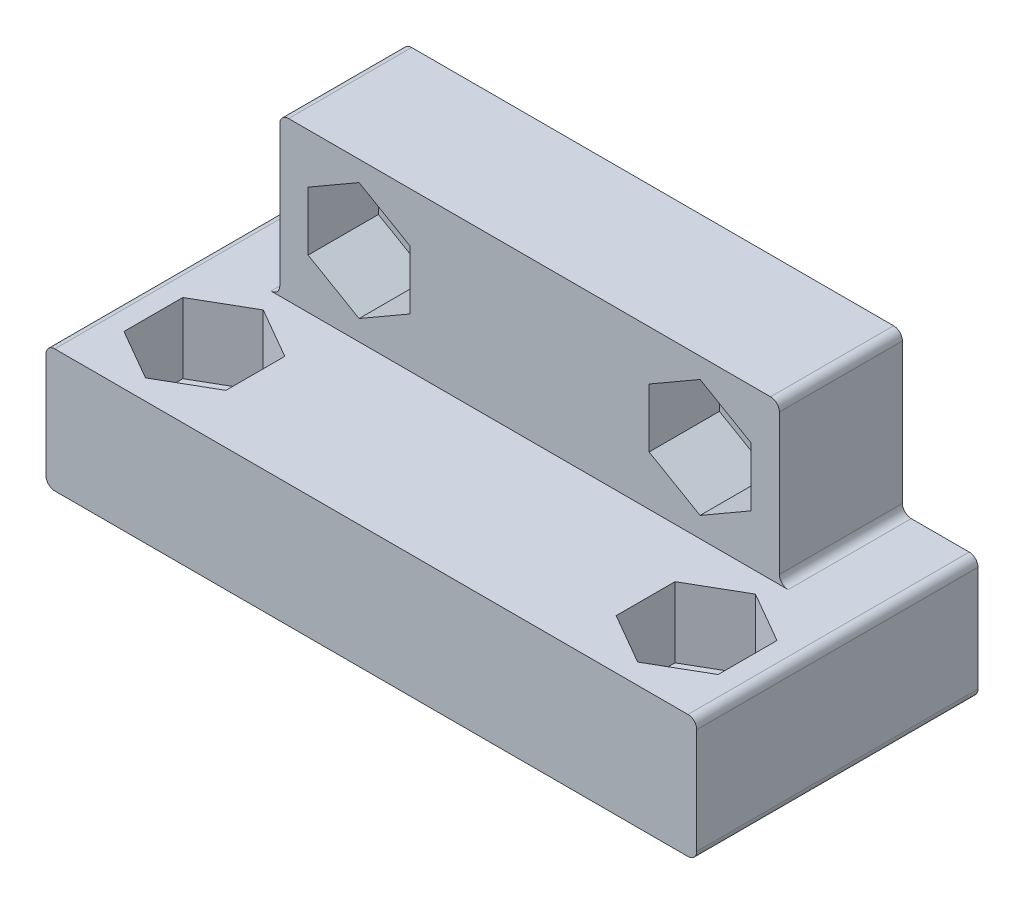
SolidWorks part; units mm, degrees
ref_plane "Front Plane" through (0, 0, 0) normal (0, 0, 1) x (1, 0, 0)
ref_plane "Top Plane" through (0, 0, 0) normal (0, 1, 0) x (1, 0, 0)
ref_plane "Right Plane" through (0, 0, 0) normal (1, 0, 0) x (0, 0, -1)
sketch "Sketch1" plane through (0, 0, 0) normal (0, 0, 1) x (1, 0, 0)
  line L30 (36.52, 7) -> (33.22, 7)
  line L31 (32.72, 7.5) -> (32.72, 15.5)
  line L32 (36.52, 0) -> (0.5, 0)
  line L33 (4.3, 7.5) -> (4.3, 15.5)
  line L34 (3.8, 7) -> (0.5, 7)
  line L35 (4.8, 16) -> (32.22, 16)
  line L36 (0, 6.5) -> (0, 0.5)
  line L37 (37.02, 0.5) -> (37.02, 6.5)
  arc A4 (0.5, 0) -> (0, 0.5) centre (0.5, 0.5) cw
  circle A12 centre (8.81, 11.5) radius 1.65
  circle A13 centre (28.21, 11.5) radius 1.65
  arc A14 (37.02, 6.5) -> (36.52, 7) centre (36.52, 6.5) ccw
  arc A15 (36.52, 0) -> (37.02, 0.5) centre (36.52, 0.5) ccw
  arc A16 (0.5, 7) -> (0, 6.5) centre (0.5, 6.5) ccw
  arc A17 (4.3, 7.5) -> (3.8, 7) centre (3.8, 7.5) cw
  arc A18 (4.3, 15.5) -> (4.8, 16) centre (4.8, 15.5) cw
  arc A19 (32.72, 15.5) -> (32.22, 16) centre (32.22, 15.5) ccw
  arc A20 (32.72, 7.5) -> (33.22, 7) centre (33.22, 7.5) ccw
extrude "Boss-Extrude1" add sketch "Sketch1" along normal blind 16
sketch "Sketch2" plane through (0, 0, 16) normal (0, 0, 1) x (1, 0, 0)
  line L0 (33.22, 7) -> (3.8, 7)
  line L5 (4.3, 16) -> (32.72, 16)
  line L6 (4.3, 16) -> (4.3, 7.5)
  line L8 (32.72, 16) -> (32.72, 7.5)
  arc A0 (3.8, 7) -> (4.3, 7.5) centre (3.8, 7.5) ccw
  arc A1 (32.72, 7.5) -> (33.22, 7) centre (33.22, 7.5) ccw
extrude "Cut-Extrude1" cut sketch "Sketch2" against normal offset from surface (9 mm away) 7 up to face at (10.46, 11.5, 0)
sketch "Sketch3" plane through (0, 0, 7) normal (0, 0, 1) x (1, 0, 0)
  line L0 (8.81, 8.1514) -> (11.71, 9.8257)
  line L1 (11.71, 9.8257) -> (11.71, 13.1743)
  line L2 (11.71, 13.1743) -> (8.81, 14.8486)
  line L3 (8.81, 14.8486) -> (5.91, 13.1743)
  line L4 (5.91, 13.1743) -> (5.91, 9.8257)
  line L5 (5.91, 9.8257) -> (8.81, 8.1514)
  line L6 (28.21, 8.1514) -> (31.11, 9.8257)
  line L7 (31.11, 9.8257) -> (31.11, 13.1743)
  line L8 (31.11, 13.1743) -> (28.21, 14.8486)
  line L9 (28.21, 14.8486) -> (25.31, 13.1743)
  line L10 (25.31, 13.1743) -> (25.31, 9.8257)
  line L11 (25.31, 9.8257) -> (28.21, 8.1514)
  circle A0 centre (8.81, 11.5) radius 2.9 construction
  circle A1 centre (28.21, 11.5) radius 2.9 construction
extrude "Cut-Extrude2" cut sketch "Sketch3" against normal offset from surface (4 mm away) 3 up to face at (10.46, 11.5, 0)
sketch "Sketch4" plane through (0, 7, 0) normal (0, 1, 0) x (1, 0, 0)
  circle A6 centre (32.51, -11.5) radius 1.65
  circle A7 centre (4.51, -11.5) radius 1.65
extrude "Cut-Extrude3" cut sketch "Sketch4" against normal up to surface (7 mm away) up to face at (18.51, 0, 8)
sketch "Sketch5" plane through (0, 7, 0) normal (0, 1, 0) x (1, 0, 0)
  line L0 (32.51, -14.8486) -> (35.41, -13.1743)
  line L1 (35.41, -13.1743) -> (35.41, -9.8257)
  line L2 (35.41, -9.8257) -> (32.51, -8.1514)
  line L3 (32.51, -8.1514) -> (29.61, -9.8257)
  line L4 (29.61, -9.8257) -> (29.61, -13.1743)
  line L5 (29.61, -13.1743) -> (32.51, -14.8486)
  line L6 (4.51, -14.8486) -> (7.41, -13.1743)
  line L7 (7.41, -13.1743) -> (7.41, -9.8257)
  line L8 (7.41, -9.8257) -> (4.51, -8.1514)
  line L9 (4.51, -8.1514) -> (1.61, -9.8257)
  line L10 (1.61, -9.8257) -> (1.61, -13.1743)
  line L11 (1.61, -13.1743) -> (4.51, -14.8486)
  circle A0 centre (32.51, -11.5) radius 2.9 construction
  circle A1 centre (4.51, -11.5) radius 2.9 construction
extrude "Cut-Extrude4" cut sketch "Sketch5" against normal offset from surface (4 mm away) 3 up to face at (30.86, 0, 11.5)
